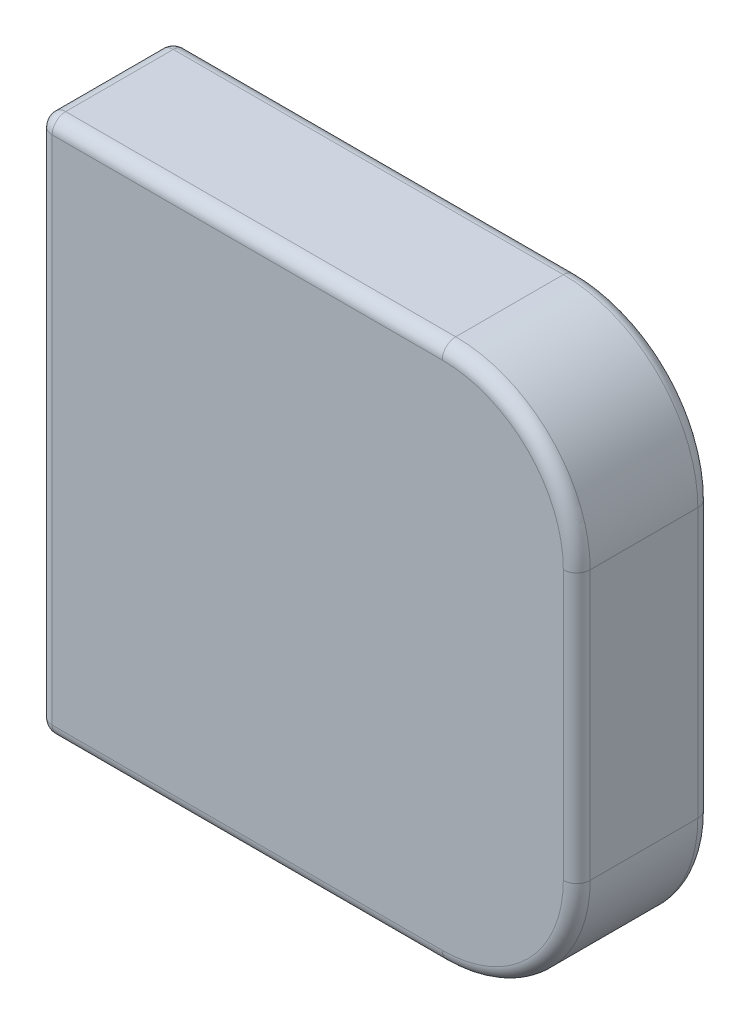
SolidWorks part; units mm, degrees
ref_plane "前视基准面" through (0, 0, 0) normal (0, 0, 1) x (1, 0, 0)
ref_plane "上视基准面" through (0, 0, 0) normal (0, 1, 0) x (1, 0, 0)
ref_plane "右视基准面" through (0, 0, 0) normal (1, 0, 0) x (0, 0, -1)
sketch "草图1" plane through (0, 0, 0) normal (0, 0, 1) x (1, 0, 0)
  line L1 (-20, -20) -> (20, -20) construction
  line L2 (-20, -20) -> (-20, 20)
  line L3 (-20, 20) -> (20, 20) construction
  line L4 (20, -20) -> (20, 20) construction
  line L5 (-20, -20) -> (20, 20) construction
  line L6 (-20, 20) -> (20, -20) construction
  line L7 (-20, 20) -> (20, 20)
  line L8 (-20, -20) -> (20, -20)
  line L9 (20, -20) -> (20, 20)
  point P0 (0, 0)
  dimension "D1" = 40
  dimension "D2" = 40
extrude "凸台-拉伸1" add sketch "草图1" along normal blind 10
sketch "草图2" plane through (0, 0, 10) normal (0, 0, 1) x (1, 0, 0)
  line L0 (0, 0) -> (50000, 0) construction
  line L7 (-10, -10) -> (-10, 10) construction
  line L8 (-10, 10) -> (15, 10) construction
  line L9 (15, -10) -> (15, 10) construction
  line L10 (-10, -10) -> (15, 10) construction
  line L11 (-10, 10) -> (15, -10) construction
  line L12 (2.5, 0) -> (2.5, 50000) construction
  line L13 (-10, -10) -> (15, -10) construction
  circle A4 centre (-10, 10) radius 1.6
  circle A5 centre (15, 10) radius 1.6
  circle A6 centre (15, -10) radius 1.6
  circle A7 centre (-10, -10) radius 1.6
  point P0 (2.5, 0)
  dimension "D3" = 2.5
  dimension "D4" = 3.2
  dimension "D1" = 20
  dimension "D2" = 25
extrude "切除-拉伸1" [suppressed] cut sketch "草图2" against normal through all
fillet "圆角1" radius 10 2 edges at (20, -20, 5) (20, 20, 5)
fillet "圆角2" radius 1 14 edges at (-5, -20, 0) (-5, -20, 10) (-20, 0, 0) (-5, 20, 0) (-5, 20, 10) (-20, 0, 10) (-20, -20, 5) (-20, 20, 5) (17.0711, -17.0711, 0) (20, 0, 0) (17.0711, 17.0711, 0) (17.0711, -17.0711, 10) (20, 0, 10) (17.0711, 17.0711, 10)
equation "\"3。2\"=3.16193"
